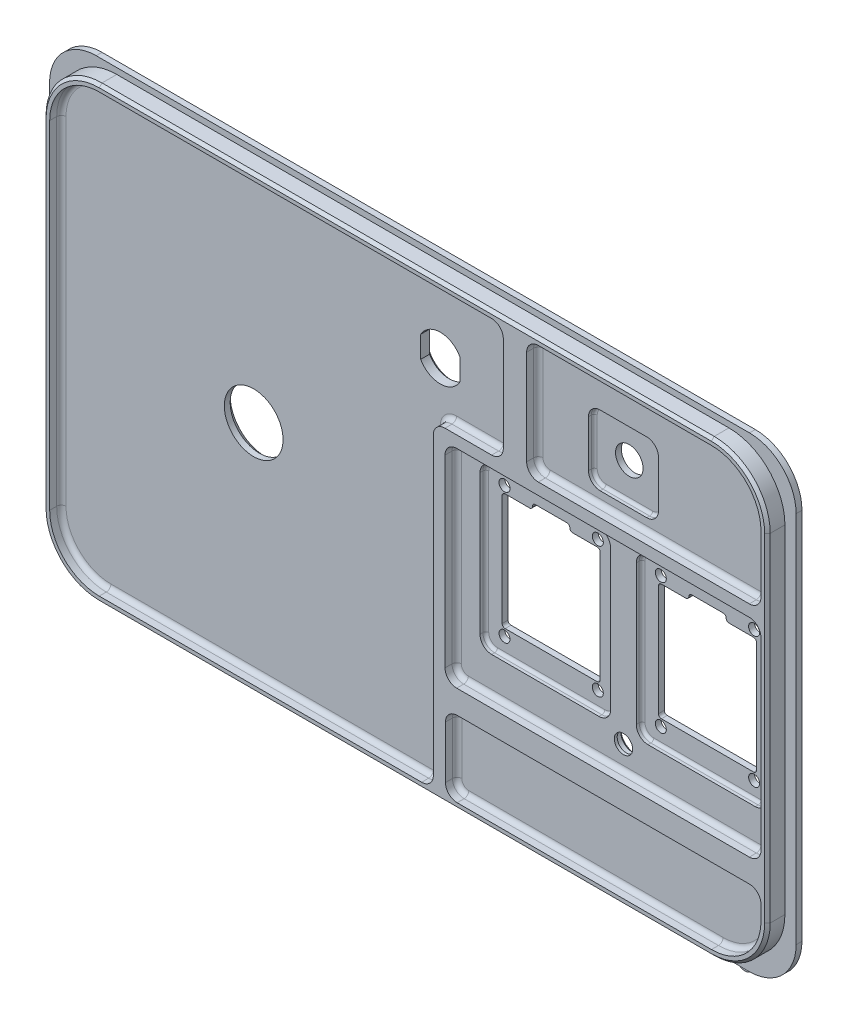
SolidWorks part; units mm, degrees
other "Markup1"
sketch "Sketch16" plane through (101.6, -64.262, 0) normal (0.6129, -0.7806, -0.1222) x (-0.7887, -0.6137, -0.0361)
ref_plane "Front Plane" through (0, 0, 0) normal (0, 0, 1) x (1, 0, 0)
ref_plane "Top Plane" through (0, 0, 0) normal (0, 1, 0) x (1, 0, 0)
ref_plane "Right Plane" through (0, 0, 0) normal (1, 0, 0) x (0, 0, -1)
sketch "Sketch2" plane through (0, 0, 0) normal (0, 0, 1) x (1, 0, 0)
  line L1 (-101.6, -63.5) -> (101.6, -63.5)
  line L2 (-101.6, -63.5) -> (-101.6, 63.5)
  line L3 (-101.6, 63.5) -> (101.6, 63.5)
  line L4 (101.6, -63.5) -> (101.6, 63.5)
  line L5 (-101.6, -63.5) -> (101.6, 63.5) construction
  line L6 (-101.6, 63.5) -> (101.6, -63.5) construction
  point P0 (0, 0)
  dimension "D1" = 203.2
  dimension "D2" = 127
extrude "Boss-Extrude1" add sketch "Sketch2" along normal blind 3.175
sketch "Sketch3" plane through (0, 0, 3.175) normal (0, 0, 1) x (1, 0, 0)
  line L0 (101.6, 63.5) -> (-101.6, 63.5) construction
  line L1 (-101.6, -63.5) -> (101.6, -63.5) construction
  line L2 (101.6, -63.5) -> (101.6, 63.5) construction
  line L3 (-101.6, 63.5) -> (-101.6, -63.5) construction
  line L21 (98.552, -45.212) -> (98.552, 46.637)
  line L22 (-83.312, -60.452) -> (83.312, -60.452)
  line L23 (-98.552, 46.637) -> (-98.552, -45.212)
  line L24 (83.312, 61.877) -> (-83.312, 61.877)
  line L25 (101.6, -63.5) -> (101.6, 63.5)
  line L26 (-101.6, -63.5) -> (101.6, -63.5)
  line L27 (-101.6, 63.5) -> (-101.6, -63.5)
  line L28 (101.6, 63.5) -> (-101.6, 63.5)
  arc A0 (83.312, 61.877) -> (98.552, 46.637) centre (83.312, 46.637) cw
  arc A1 (83.312, -60.452) -> (98.552, -45.212) centre (83.312, -45.212) ccw
  arc A2 (-83.312, -60.452) -> (-98.552, -45.212) centre (-83.312, -45.212) cw
  arc A3 (-98.552, 46.637) -> (-83.312, 61.877) centre (-83.312, 46.637) cw
  dimension "D2" = 15.24
  dimension "D1" = 1.623
  dimension "D3" = 3.048
  dimension "D4" = 3.048
  dimension "D5" = 3.048
extrude "Cut-Extrude1" cut sketch "Sketch3" against normal blind 1.5875
fillet "Fillet1" radius 12.7 4 edges at (101.6, 63.5, 0.7937) (-101.6, 63.5, 0.7937) (-101.6, -63.5, 0.7937) (101.6, -63.5, 0.7937)
sketch "Sketch13" plane through (0, 0, 3.175) normal (0, 0, 1) x (1, 0, 0)
  line L21 (98.552, -45.212) -> (98.552, 46.637) construction
  line L22 (83.312, 61.877) -> (-83.312, 61.877) construction
  line L23 (-98.552, 46.637) -> (-98.552, -45.212) construction
  line L24 (-83.312, -60.452) -> (83.312, -60.452) construction
  line L25 (96.802, -45.212) -> (96.802, 46.637)
  line L26 (-83.312, -58.702) -> (83.312, -58.702)
  line L27 (-96.802, 46.637) -> (-96.802, -45.212)
  line L28 (83.312, 60.127) -> (-83.312, 60.127)
  line L29 (96.802, -45.212) -> (96.802, 46.637)
  line L30 (-83.312, -58.702) -> (83.312, -58.702)
  line L31 (-96.802, 46.637) -> (-96.802, -45.212)
  line L32 (83.312, 60.127) -> (-83.312, 60.127)
  line L33 (98.552, -45.212) -> (98.552, 46.637)
  line L34 (83.312, 61.877) -> (-83.312, 61.877)
  line L35 (-98.552, 46.637) -> (-98.552, -45.212)
  line L36 (-83.312, -60.452) -> (83.312, -60.452)
  arc A15 (98.552, 46.637) -> (83.312, 61.877) centre (83.312, 46.637) ccw construction
  arc A16 (-83.312, 61.877) -> (-98.552, 46.637) centre (-83.312, 46.637) ccw construction
  arc A17 (-98.552, -45.212) -> (-83.312, -60.452) centre (-83.312, -45.212) ccw construction
  arc A18 (83.312, -60.452) -> (98.552, -45.212) centre (83.312, -45.212) ccw construction
  arc A19 (96.802, 46.637) -> (83.312, 60.127) centre (83.312, 46.637) ccw
  arc A20 (83.312, -58.702) -> (96.802, -45.212) centre (83.312, -45.212) ccw
  arc A21 (-96.802, -45.212) -> (-83.312, -58.702) centre (-83.312, -45.212) ccw
  arc A22 (-83.312, 60.127) -> (-96.802, 46.637) centre (-83.312, 46.637) ccw
  arc A23 (96.802, 46.637) -> (83.312, 60.127) centre (83.312, 46.637) ccw
  arc A24 (83.312, -58.702) -> (96.802, -45.212) centre (83.312, -45.212) ccw
  arc A25 (-96.802, -45.212) -> (-83.312, -58.702) centre (-83.312, -45.212) ccw
  arc A26 (-83.312, 60.127) -> (-96.802, 46.637) centre (-83.312, 46.637) ccw
  arc A27 (98.552, 46.637) -> (83.312, 61.877) centre (83.312, 46.637) ccw
  arc A28 (-83.312, 61.877) -> (-98.552, 46.637) centre (-83.312, 46.637) ccw
  arc A29 (-98.552, -45.212) -> (-83.312, -60.452) centre (-83.312, -45.212) ccw
  arc A30 (83.312, -60.452) -> (98.552, -45.212) centre (83.312, -45.212) ccw
  dimension "D1" = 1.75
extrude "Boss-Extrude2" add sketch "Sketch13" along normal blind 3.175
sketch "Sketch4" plane through (0, 0, 0) normal (0, 0, -1) x (-1, 0, 0)
  arc A0 (41.4517, 43.8396) -> (0.6104, 2.9983) centre (44.45, 0) ccw
  arc A1 (88.2896, -2.9983) -> (88.2896, 2.9983) centre (88.392, 0) ccw
  arc A2 (0.6104, 2.9983) -> (0.6104, -2.9983) centre (0.508, 0) ccw
  arc A3 (47.4483, 43.8396) -> (41.4517, 43.8396) centre (44.45, 43.942) ccw
  arc A4 (41.4517, -43.8396) -> (47.4483, -43.8396) centre (44.45, -43.942) ccw
  arc A5 (88.2896, 2.9983) -> (47.4483, 43.8396) centre (44.45, 0) ccw
  arc A6 (47.4483, -43.8396) -> (88.2896, -2.9983) centre (44.45, 0) ccw
  arc A7 (0.6104, -2.9983) -> (41.4517, -43.8396) centre (44.45, 0) ccw
  dimension "D1" = 87.884
  dimension "D3" = 3
  dimension "D2" = 44.45
extrude "big_BUTTON_HOLE" [suppressed] cut sketch "Sketch4" against normal through all
sketch "Sketch9" plane through (0, 0, 0) normal (0, 0, 1) x (1, 0, 0)
  circle A0 centre (-44.45, 0) radius 8
  dimension "D1" = 16
  dimension "D2" = 44.45
sketch "Sketch5" plane through (0, 0, 0) normal (0, 0, -1) x (-1, 0, 0)
  line L0 (-101.6, -50.8) -> (-101.6, 50.8) construction
  line L1 (-82.55, 15.875) -> (-82.55, 17.4625)
  line L2 (-77.47, 5.2299) -> (-77.47, -39.4161) construction
  line L3 (-34.925, 5.2299) -> (-34.925, -38.0723) construction
  line L4 (-82.55, 17.4625) -> (-72.39, 17.4625)
  line L5 (-90.805, 15.875) -> (-82.55, 15.875)
  line L6 (-90.805, 15.875) -> (-90.805, -15.875)
  line L8 (-64.135, 15.875) -> (-64.135, -15.875)
  line L9 (-90.805, 15.875) -> (-64.135, -15.875) construction
  line L10 (-90.805, -15.875) -> (-64.135, 15.875) construction
  line L11 (-48.26, 15.875) -> (-40.005, 15.875)
  line L12 (-48.26, 15.875) -> (-48.26, -15.875)
  line L14 (-21.59, 15.875) -> (-21.59, -15.875)
  line L15 (-48.26, 15.875) -> (-21.59, -15.875) construction
  line L16 (-48.26, -15.875) -> (-21.59, 15.875) construction
  line L17 (-72.39, 17.4625) -> (-72.39, 15.875)
  line L18 (-72.39, 15.875) -> (-64.135, 15.875)
  line L19 (-40.005, 15.875) -> (-40.005, 17.4625)
  line L20 (-40.005, 17.4625) -> (-29.845, 17.4625)
  line L21 (-29.845, 17.4625) -> (-29.845, 15.875)
  line L30 (-29.845, 15.875) -> (-21.59, 15.875)
  line L34 (-90.805, -15.875) -> (-64.135, -15.875)
  line L35 (-48.26, -15.875) -> (-21.59, -15.875)
  circle A0 centre (-22.225, -17.78) radius 1.5
  circle A1 centre (-47.625, -17.78) radius 1.5
  circle A2 centre (-22.225, 17.78) radius 1.5
  circle A3 centre (-47.625, 17.78) radius 1.5
  circle A4 centre (-64.77, -17.78) radius 1.5
  circle A5 centre (-64.77, 17.78) radius 1.5
  circle A6 centre (-90.17, -17.78) radius 1.5
  circle A7 centre (-90.17, 17.78) radius 1.5
  circle A8 centre (-56.1975, 40.64) radius 3.75
  circle A9 centre (-56.1975, -25.4) radius 2.5
  point P18 (-77.47, 0)
  point P23 (-34.925, 0)
  point P40 (-77.47, 17.4625)
  point P53 (-34.925, 17.4625)
  dimension "D7" = 3
  dimension "D13" = 7.5
  dimension "D15" = 5
  dimension "D1" = 25.4
  dimension "D2" = 25.4
  dimension "D3" = 35.56
  dimension "D4" = 17.145
  dimension "D5" = 11.43
  dimension "D6" = 40.64
  dimension "D8" = 12.7
  dimension "D9" = 12.7
  dimension "D10" = 31.75
  dimension "D11" = 26.67
  dimension "D12" = 1.905
  dimension "D14" = 8.5725
  dimension "D16" = 25.4
  dimension "D17" = 10.16
  dimension "D18" = 1.5875
  dimension "D19" = 26.67
extrude "OLED_CUTOUT" cut sketch "Sketch5" against normal through all
chamfer "Chamfer1" [suppressed] distance 1.5875 angle 45
sketch "Sketch8" plane through (0, 0, 0) normal (0, 0, -1) x (-1, 0, 0)
  line L0 (-1.016, 37.6888) -> (-1.016, 43.5912)
  line L1 (-11.684, 37.6888) -> (-11.684, 43.5912)
  arc A0 (-1.016, 43.5912) -> (-11.684, 43.5912) centre (-6.35, 40.64) ccw
  arc A1 (-11.684, 37.6888) -> (-1.016, 37.6888) centre (-6.35, 40.64) ccw
  dimension "D1" = 6.096
  dimension "D2" = 10.668
  dimension "D3" = 5.334
  dimension "D4" = 6.35
  dimension "D5" = 40.64
extrude "Key_switch" cut sketch "Sketch8" against normal through all
extrude "small_button" cut sketch "Sketch9" along normal through all
sketch "Sketch10" plane through (0, 0, 0) normal (0, 0, -1) x (-1, 0, 0)
  circle A0 centre (-56.1975, -25.4) radius 3.125
  dimension "D1" = 6.25
extrude "Cut-Extrude4" cut sketch "Sketch10" against normal blind 2.3812
sketch "Sketch11" plane through (0, 0, 3.175) normal (0, 0, 1) x (1, 0, 0)
  line L1 (46.6725, 50.165) -> (65.7225, 50.165)
  line L2 (46.6725, 50.165) -> (46.6725, 31.115)
  line L3 (46.6725, 31.115) -> (65.7225, 31.115)
  line L4 (65.7225, 50.165) -> (65.7225, 31.115)
  line L5 (46.6725, 50.165) -> (65.7225, 31.115) construction
  line L6 (46.6725, 31.115) -> (65.7225, 50.165) construction
  point P0 (56.1975, 40.64)
  dimension "D1" = 19.05
  dimension "D2" = 19.05
extrude "Cut-Extrude5" cut sketch "Sketch11" against normal blind 1.5875
sketch "Sketch12" plane through (0, 0, 3.175) normal (0, 0, 1) x (1, 0, 0)
  line L0 (34.925, 17.4625) -> (34.925, -24.701) construction
  line L1 (17.145, -22.225) -> (52.705, -22.225)
  line L2 (17.145, -22.225) -> (17.145, 22.225)
  line L3 (17.145, 22.225) -> (52.705, 22.225)
  line L4 (52.705, -22.225) -> (52.705, 22.225)
  line L5 (17.145, -22.225) -> (52.705, 22.225) construction
  line L6 (17.145, 22.225) -> (52.705, -22.225) construction
  line L7 (95.25, 22.225) -> (59.69, 22.225)
  line L8 (95.25, 22.225) -> (95.25, -22.225)
  line L9 (95.25, -22.225) -> (59.69, -22.225)
  line L10 (59.69, 22.225) -> (59.69, -22.225)
  line L11 (95.25, 22.225) -> (59.69, -22.225) construction
  line L12 (95.25, -22.225) -> (59.69, 22.225) construction
  line L13 (29.845, 17.4625) -> (40.005, 17.4625) construction
  line L14 (0, 0) -> (93.7193, 0) construction
  line L15 (77.47, 17.4625) -> (77.47, -24.701) construction
  line L16 (72.39, 17.4625) -> (82.55, 17.4625) construction
  point P0 (34.925, 0)
  point P5 (77.47, 0)
  dimension "D1" = 44.45
  dimension "D2" = 35.56
extrude "Cut-Extrude6" cut sketch "Sketch12" against normal blind 1.5875
fillet "Fillet7" radius 0.7937 16 edges at (90.805, 15.875, 0.7938) (82.55, 15.875, 0.7938) (82.55, 17.4625, 0.7938) (64.135, 15.875, 0.7938) (72.39, 17.4625, 0.7938) (72.39, 15.875, 0.7938) (48.26, 15.875, 0.7938) (40.005, 17.4625, 0.7938) (29.845, 17.4625, 0.7938) (21.59, 15.875, 0.7938) (40.005, 15.875, 0.7938) (29.845, 15.875, 0.7938) (21.59, -15.875, 0.7938) (48.26, -15.875, 0.7938) (64.135, -15.875, 0.7938) (90.805, -15.875, 0.7938)
chamfer "Chamfer2" distance 1.5875 angle 45 1 edges at (-36.45, 0, 0)
fillet "Fillet8" radius 3.175 12 edges at (95.25, 22.225, 2.3812) (59.69, 22.225, 2.3812) (59.69, -22.225, 2.3812) (95.25, -22.225, 2.3812) (52.705, -22.225, 2.3812) (17.145, -22.225, 2.3812) (52.705, 22.225, 2.3812) (17.145, 22.225, 2.3812) (65.7225, 31.115, 2.3812) (46.6725, 31.115, 2.3812) (65.7225, 50.165, 2.3812) (46.6725, 50.165, 2.3812)
fillet "Fillet9" radius 0.7937 24 edges at (47.6024, 49.2351, 1.5875) (56.1975, 50.165, 1.5875) (64.7926, 49.2351, 1.5875) (65.7225, 40.64, 1.5875) (64.7926, 32.0449, 1.5875) (56.1975, 31.115, 1.5875) (47.6024, 32.0449, 1.5875) (34.925, 22.225, 1.5875) (51.7751, 21.2951, 1.5875) (52.705, 0, 1.5875) (51.7751, -21.2951, 1.5875) (34.925, -22.225, 1.5875) (18.0749, -21.2951, 1.5875) (17.145, 0, 1.5875) (46.6725, 40.64, 1.5875) (18.0749, 21.2951, 1.5875) (94.3201, 21.2951, 1.5875) (95.25, 0, 1.5875) (94.3201, -21.2951, 1.5875) (77.47, -22.225, 1.5875) (60.6199, -21.2951, 1.5875) (59.69, 0, 1.5875) (60.6199, 21.2951, 1.5875) (77.47, 22.225, 1.5875)
chamfer "Chamfer3" distance 0.762 angle 45 8 edges at (0, -60.452, 6.35) (94.0883, -55.9883, 6.35) (-94.0883, -55.9883, 6.35) (98.552, 0.7125, 6.35) (-98.552, 0.7125, 6.35) (94.0883, 57.4133, 6.35) (-94.0883, 57.4133, 6.35) (0, 61.877, 6.35)
sketch "Sketch14" plane through (0, 0, 0) normal (0, 0, -1) x (-1, 0, 0)
  line L0 (-88.9, -63.5) -> (-88.9, -64.262)
  line L1 (-88.9, -64.262) -> (-85.725, -64.262)
  line L2 (-85.725, -64.262) -> (-85.725, -63.5)
  line L3 (88.9, -63.5) -> (-88.9, -63.5) construction
  line L4 (-85.725, -63.5) -> (-88.9, -63.5)
  point P9 (-85.725, -64.262)
  point P12 (-88.9, -64.262)
  dimension "D1" = 0.762
  dimension "D2" = 3.175
extrude "Boss-Extrude3" add sketch "Sketch14" against normal blind 1.27
mirror "Mirror1" about plane through (0, 0, 0) normal (1, 0, 0) of "Boss-Extrude3"
fillet "Fillet12" radius 1.5875 4 edges at (-85.725, -64.262, 0.635) (-88.9, -64.262, 0.635) (85.725, -64.262, 0.635) (88.9, -64.262, 0.635)
sketch "Sketch15" plane through (0, 0, 3.175) normal (0, 0, 1) x (1, 0, 0)
  line L0 (96.802, -45.212) -> (96.802, 46.637) construction
  line L1 (96.802, 27.94) -> (33.02, 27.94)
  line L2 (96.802, 27.94) -> (96.802, 24.765)
  line L3 (96.802, -38.1) -> (10.922, -38.1)
  line L4 (7.62, 27.94) -> (7.62, -58.702)
  line L5 (96.802, 24.765) -> (10.795, 24.765)
  line L6 (10.795, 24.765) -> (10.795, -31.75)
  line L7 (10.795, -31.75) -> (96.802, -31.75)
  line L8 (96.802, -31.75) -> (96.802, -38.1)
  line L9 (88.9, 63.5) -> (-88.9, 63.5) construction
  line L11 (-83.312, -58.702) -> (83.312, -58.702) construction
  line L12 (10.922, -38.1) -> (10.922, -58.702)
  line L13 (10.922, -58.702) -> (7.62, -58.702)
  line L14 (26.67, 60.127) -> (26.67, 27.94)
  line L15 (83.312, 60.127) -> (-83.312, 60.127) construction
  line L16 (33.02, 60.127) -> (33.02, 27.94)
  line L18 (26.67, 60.127) -> (33.02, 60.127)
  line L19 (26.67, 27.94) -> (7.62, 27.94)
  line L20 (101.6, -50.8) -> (101.6, 50.8) construction
  line L21 (-88.9, -63.5) -> (88.9, -63.5) construction
  dimension "D1" = 3.175
  dimension "D2" = 35.56
  dimension "D3" = 6.35
  dimension "D4" = 3.175
  dimension "D5" = 3.302
  dimension "D6" = 6.35
  dimension "D7" = 68.58
  dimension "D8" = 25.4
  dimension "D9" = 93.98
extrude "Boss-Extrude5" add sketch "Sketch15" along direction (0, 0, 1) on the side of the normal blind 3.175
fillet "Fillet13" radius 3.175 14 edges at (26.67, 60.127, 4.7625) (26.67, 27.94, 4.7625) (7.62, 27.94, 4.7625) (96.802, -38.1, 4.7625) (10.922, -38.1, 4.7625) (10.922, -58.702, 4.7625) (33.02, 60.127, 4.7625) (33.02, 27.94, 4.7625) (96.802, 27.94, 4.7625) (96.802, -31.75, 4.7625) (96.802, 24.765, 4.7625) (10.795, -31.75, 4.7625) (10.795, 24.765, 4.7625) (7.62, -58.702, 4.7625)
fillet "Fillet14" radius 1.27 36 edges at (-39.4335, -58.702, 3.175) (-92.8509, -54.7509, 3.175) (-96.802, 0.7125, 3.175) (-92.8509, 56.1759, 3.175) (-29.9085, 60.127, 3.175) (25.7401, 59.1971, 3.175) (26.67, 44.0335, 3.175) (25.7401, 28.8699, 3.175) (17.145, 27.94, 3.175) (8.5499, 27.0101, 3.175) (11.8519, -39.0299, 3.175) (10.922, -48.401, 3.175) (11.8519, -57.7721, 3.175) (48.7045, -58.702, 3.175) (92.8509, -54.7509, 3.175) (96.802, -43.2435, 3.175) (95.8721, -39.0299, 3.175) (11.7249, 23.8351, 3.175) (10.795, -3.4925, 3.175) (11.7249, -30.8201, 3.175) (53.7985, -31.75, 3.175) (95.8721, -30.8201, 3.175) (96.802, -3.4925, 3.175) (95.8721, 23.8351, 3.175) (92.8509, 56.1759, 3.175) (96.802, 38.876, 3.175) (95.8721, 28.8699, 3.175) (64.911, 27.94, 3.175) (33.9499, 28.8699, 3.175) (33.02, 44.0335, 3.175) (33.9499, 59.1971, 3.175) (7.62, -15.381, 3.175) (53.862, -38.1, 3.175) (53.7985, 24.765, 3.175) (59.7535, 60.127, 3.175) (6.6901, -57.7721, 3.175)
chamfer "Chamfer4" distance 0.762 angle 45 1 edges at (53.0725, -25.4, 0)
chamfer "Chamfer5" distance 0.762 angle 45 4 edges at (6.35, 46.736, 0) (11.684, 40.64, 0) (1.016, 40.64, 0) (6.35, 34.544, 0)
fillet "Fillet15" [suppressed] radius 0.7937
equation "\".0750.100000in\"=0.1"
